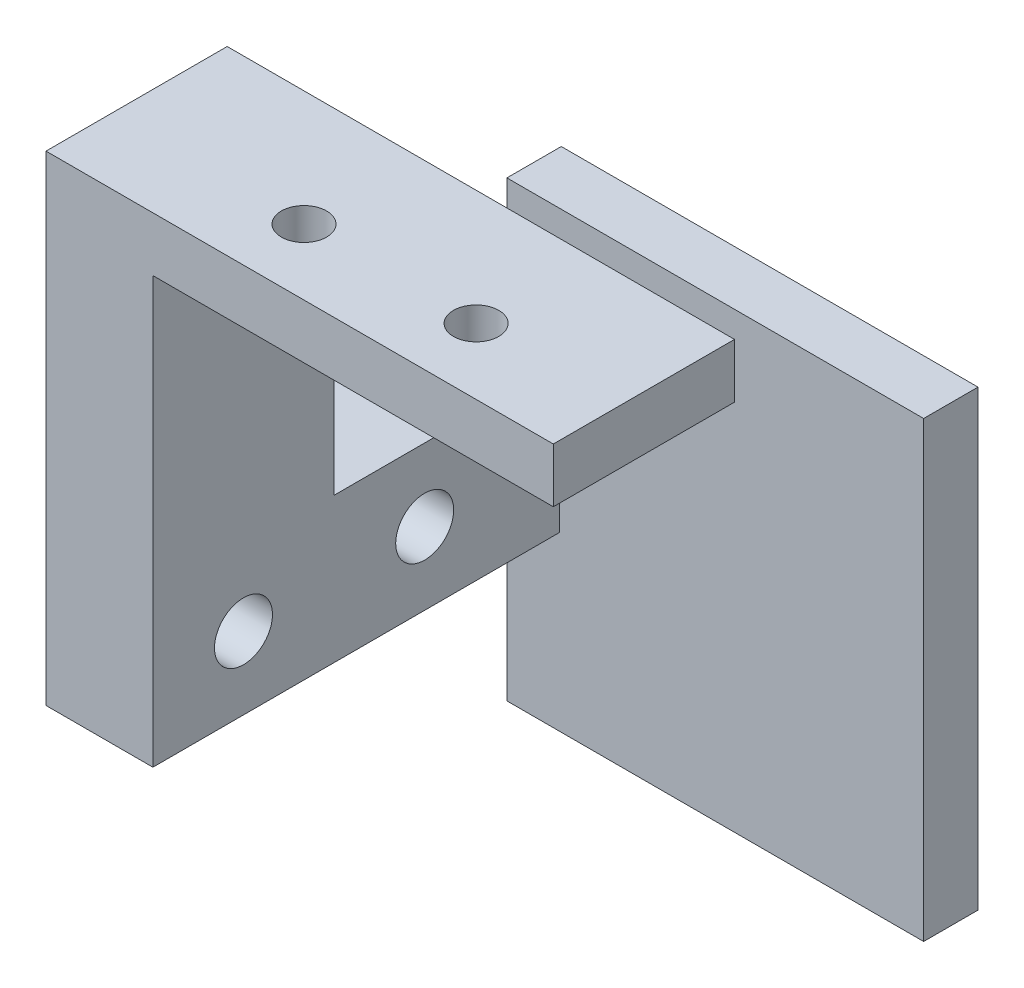
SolidWorks part; units mm, degrees
ref_plane "Front Plane" through (0, 0, 0) normal (0, 0, 1) x (1, 0, 0)
ref_plane "Top Plane" through (0, 0, 0) normal (0, 1, 0) x (1, 0, 0)
ref_plane "Right Plane" through (0, 0, 0) normal (1, 0, 0) x (0, 0, -1)
sketch "Sketch1" plane through (0, 0, 0) normal (0, 1, 0) x (1, 0, 0)
  line L1 (-12.5, -5) -> (12.5, -5)
  line L2 (-12.5, -5) -> (-12.5, 5)
  line L3 (-12.5, 5) -> (12.5, 5)
  line L4 (12.5, -5) -> (12.5, 5)
  line L5 (-12.5, -5) -> (12.5, 5) construction
  line L6 (-12.5, 5) -> (12.5, -5) construction
  point P0 (0, 0)
extrude "Boss-Extrude1" add sketch "Sketch1" along normal blind 3
sketch "Sketch2" plane through (0, 3, 0) normal (0, 1, 0) x (1, 0, 0)
  circle A0 centre (-4.8941, -1.3669) radius 1.25
  circle A1 centre (4.6059, -1.3669) radius 1.25
extrude "Cut-Extrude1" cut sketch "Sketch2" against normal blind 10
sketch "Sketch3" plane through (-12.5, 0, 0) normal (-1, 0, 0) x (0, 0, 1)
  line L1 (-5, 0) -> (5, 0)
  line L2 (-5, 0) -> (-5, 3)
  line L3 (-5, 3) -> (5, 3)
  line L4 (5, 0) -> (5, 3)
extrude "Boss-Extrude2" add sketch "Sketch3" along normal blind 3
sketch "Sketch4" plane through (0, 0, -5) normal (0, 0, -1) x (-1, 0, 0)
  line L1 (15.5, 0) -> (12.5, 0)
  line L2 (15.5, 0) -> (15.5, -19.36)
  line L3 (15.5, -19.36) -> (12.5, -19.36)
  line L4 (12.5, 0) -> (12.5, -19.36)
extrude "Boss-Extrude3" add sketch "Sketch4" against normal blind 10
sketch "Sketch5" plane through (-15.5, 0, 0) normal (-1, 0, 0) x (0, 0, 1)
  line L0 (5, -19.36) -> (5, -22.36)
  line L1 (5, -22.36) -> (-17.4391, -22.36)
  line L2 (-17.4391, -31.8598) -> (-17.4391, -6.8602) construction
  line L4 (-17.4391, -19.36) -> (5, -19.36)
  line L5 (-17.4391, -19.36) -> (-20.4391, -19.36)
  line L6 (-20.4391, -19.36) -> (-20.4391, -22.36)
  line L7 (-20.4391, -22.36) -> (-17.4391, -22.36)
extrude "Boss-Extrude4" add sketch "Sketch5" against normal blind 3
sketch "Sketch6" plane through (-12.5, 0, 0) normal (1, 0, 0) x (0, 0, -1)
  line L1 (17.4391, -31.8598) -> (20.4391, -31.8598)
  line L2 (17.4391, -31.8598) -> (17.4391, -6.8598)
  line L3 (17.4391, -6.8598) -> (20.4391, -6.8598)
  line L4 (20.4391, -31.8598) -> (20.4391, -6.8598)
extrude "Boss-Extrude5" add sketch "Sketch6" along normal blind 23
sketch "Sketch7" plane through (0, -19.36, 0) normal (0, 1, 0) x (1, 0, 0)
  line L1 (-15.5, 5) -> (-12.5, 5)
  line L2 (-15.5, 5) -> (-15.5, 20.439)
  line L3 (-15.5, 20.439) -> (-12.5, 20.439)
  line L4 (-12.5, 5) -> (-12.5, 20.439)
extrude "Boss-Extrude6" add sketch "Sketch7" along normal blind 5
sketch "Sketch8" plane through (-12.5, 0, 0) normal (1, 0, 0) x (0, 0, -1)
  line L0 (17.4391, -22.36) -> (-5, -22.36)
  line L1 (-5, -22.36) -> (-5, 0)
  line L2 (-5, 0) -> (5, 0)
  line L3 (5, 0) -> (5, -14.36)
  line L4 (5, -14.36) -> (17.4391, -14.36)
  line L5 (17.4391, -14.36) -> (17.4391, -22.36)
extrude "Boss-Extrude7" add sketch "Sketch8" along normal blind 2.9
sketch "Sketch9" plane through (0, 0, -5) normal (0, 0, -1) x (-1, 0, 0)
  line L2 (1, 1.1402) -> (15.5, 1.1402)
  line L3 (15.5, 3) -> (15.5, -19.36) construction
  line L4 (15.5, 1.1402) -> (15.5, 4.1402)
  line L5 (1, 1.1402) -> (-12.5, 1.1402)
  line L6 (-12.5, 3) -> (-12.5, 0) construction
  line L7 (-12.5, 1.1402) -> (-12.5, 4.1402)
  line L8 (-12.5, 4.1402) -> (15.5, 4.1402)
extrude "Boss-Extrude8" add sketch "Sketch9" against normal blind 10
sketch "Sketch10" plane through (0, 0, -5) normal (0, 0, -1) x (-1, 0, 0)
  line L4 (-10.4648, 1.14) -> (9.6, 1.14)
  line L5 (9.6, 1.14) -> (9.6, 0)
  line L6 (9.6, 0) -> (-12.5, 0)
  line L7 (-12.5, 0) -> (-12.5, 1.14)
  line L8 (-12.5, 4.1402) -> (-12.5, 0) construction
  line L9 (-12.5, 1.14) -> (-10.4648, 1.14)
extrude "Cut-Extrude2" cut sketch "Sketch10" against normal blind 10
sketch "Sketch11" plane through (0, 1.14, 0) normal (0, -1, 0) x (1, 0, 0)
  circle A0 centre (-4.8941, 1.3669) radius 1.25
  circle A1 centre (4.6059, 1.3669) radius 1.25
extrude "Cut-Extrude3" cut sketch "Sketch11" against normal through all both and the other way through all
sketch "Sketch12" plane through (-15.5, 0, 0) normal (-1, 0, 0) x (0, 0, 1)
  circle A0 centre (0, -18.36) radius 1.6
  circle A1 centre (-10, -18.36) radius 1.6
extrude "Cut-Extrude4" cut sketch "Sketch12" against normal blind 40
